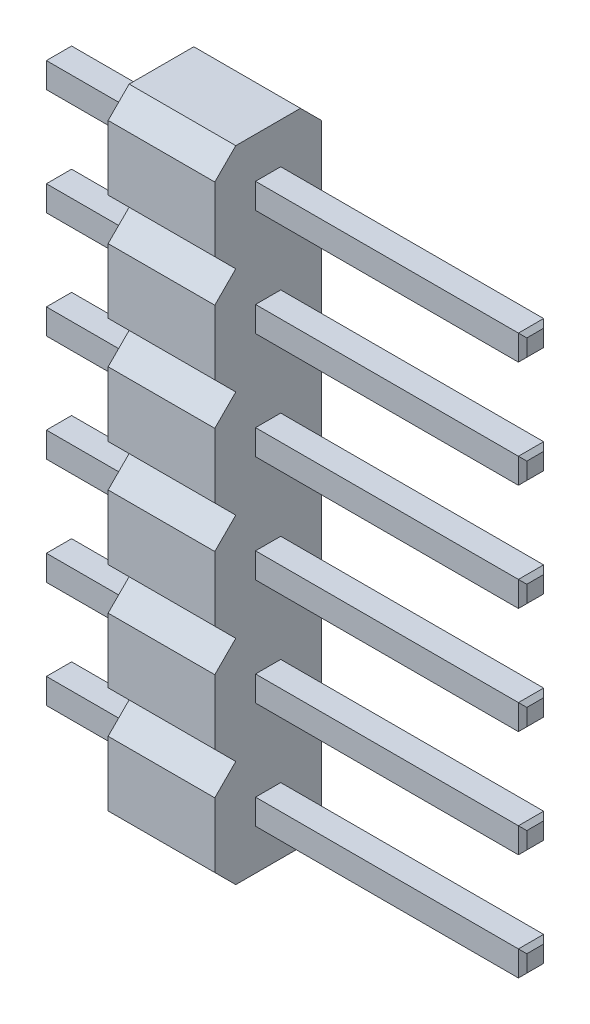
SolidWorks part; units mm, degrees
ref_plane "Front Plane" through (0, 0, 0) normal (0, 0, 1) x (1, 0, 0)
ref_plane "Top Plane" through (0, 0, 0) normal (0, 1, 0) x (1, 0, 0)
ref_plane "Right Plane" through (0, 0, 0) normal (1, 0, 0) x (0, 0, -1)
sketch "Sketch1" plane through (0, 0, 0) normal (1, 0, 0) x (0, 0, -1)
  line L0 (0, 0) -> (-1.27, 0) construction
  line L5 (-1.27, 0) -> (-1.27, 1.27) construction
  line L6 (-2.04, 1.27) -> (-0.5, 1.27)
  line L7 (-0.5, 1.27) -> (0, 0.77)
  line L8 (0, 0.77) -> (0, -0.77)
  line L9 (-2.54, 0.77) -> (-2.54, -0.77)
  line L10 (-2.04, 1.27) -> (-2.54, 0.77)
  line L11 (-0.5, -1.27) -> (0, -0.77)
  line L12 (-2.04, -1.27) -> (-0.5, -1.27)
  line L13 (-2.04, -1.27) -> (-2.54, -0.77)
  point P13 (-2.54, 0)
  dimension "D1" = 1.27
  dimension "D2" = 45
  dimension "D3" = 0.5
extrude "Plastic" add sketch "Sketch1" along normal blind 2.54
sketch "Sketch2" plane through (0, 0, 0) normal (0, 1, 0) x (1, 0, 0)
  line L0 (-2.54, -0.97) -> (-2.54, -1.57)
  line L1 (-2.54, -1.27) -> (8.9, -1.27) construction
  line L2 (0, -2.04) -> (0, -0.5) construction
  line L4 (-2.54, -1.57) -> (8.9, -1.57)
  line L6 (-2.54, -0.97) -> (8.9, -0.97)
  line L8 (8.9, -1.57) -> (8.9, -0.97)
  line L11 (-3.14, 3.36) -> (-3.14, -0.67) construction
  line L12 (-3.44, 3.36) -> (-3.44, -0.67) construction
  line L13 (-2.84, 3.36) -> (-2.84, -0.67) construction
  line L14 (2.54, -0.5) -> (2.54, -2.04) construction
  arc A3 (-3.44, -0.67) -> (-2.54, -1.57) centre (-2.54, -0.67) ccw construction
  arc A4 (-3.14, -0.67) -> (-2.54, -1.27) centre (-2.54, -0.67) ccw construction
  arc A5 (-2.84, -0.67) -> (-2.54, -0.97) centre (-2.54, -0.67) ccw construction
  point P5 (0, -1.27)
  dimension "D1" = 5.08
  dimension "D4" = 8.9
  dimension "D2" = 0.3
  dimension "D3" = 0.3
extrude "Contact" add sketch "Sketch2" along normal mid plane 0.6
chamfer "Chamfer1" distance 0.1 angle 45 8 edges at (8.9, 0.3, 1.27) (8.9, 0, 1.57) (8.9, -0.3, 1.27) (8.9, 0, 0.97) (-2.54, -0.3, 1.27) (-2.54, 0, 0.97) (-2.54, 0.3, 1.27) (-2.54, 0, 1.57)
pattern_linear "LPattern1" count 6 spacing 2.54 along (0, 1, 0) of "Plastic", "Contact", "Chamfer1"
sketch "Sketch3" plane through (8.9, 0, 0) normal (1, 0, 0) x (0, 0, -1)
  line L0 (-1.47, 12.7) -> (-1.27, 12.7) construction
  line L1 (-1.47, 12.9) -> (-1.47, 12.5) construction
  line L2 (-1.27, 12.7) -> (-1.27, 12.9) construction
  line L3 (-1.07, 12.9) -> (-1.47, 12.9) construction
ref_axis "Axis1" through (8.9, 12.7, 1.27) along (-1, 0, 0)
